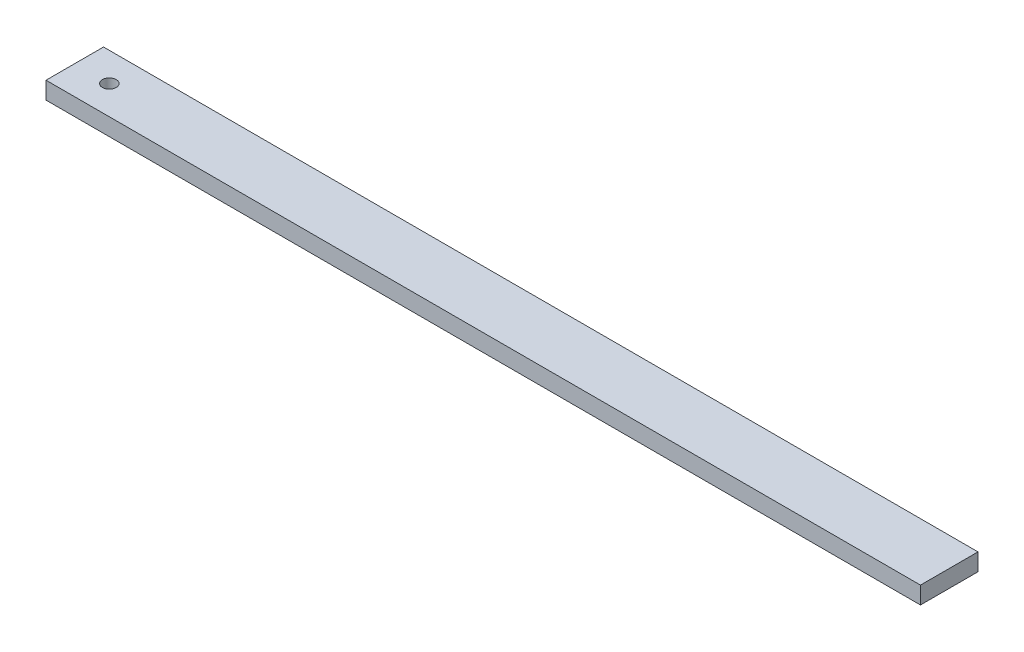
SolidWorks part; units mm, degrees
ref_plane "Front Plane" through (0, 0, 0) normal (0, 0, 1) x (1, 0, 0)
ref_plane "Top Plane" through (0, 0, 0) normal (0, 1, 0) x (1, 0, 0)
ref_plane "Right Plane" through (0, 0, 0) normal (1, 0, 0) x (0, 0, -1)
sketch "Sketch1" plane through (0, 0, 0) normal (0, 1, 0) x (1, 0, 0)
  line L1 (-9.525, -7.9375) -> (231.775, -7.9375)
  line L2 (-9.525, -7.9375) -> (-9.525, 7.9375)
  line L3 (-9.525, 7.9375) -> (231.775, 7.9375)
  line L4 (231.775, -7.9375) -> (231.775, 7.9375)
  circle A0 centre (0, 0) radius 1.905
  dimension "D5" = 3.81
  dimension "D1" = 241.3
  dimension "D2" = 15.875
  dimension "D3" = 7.9375
  dimension "D4" = 9.525
extrude "Boss-Extrude1" add sketch "Sketch1" along normal blind 4.7625
